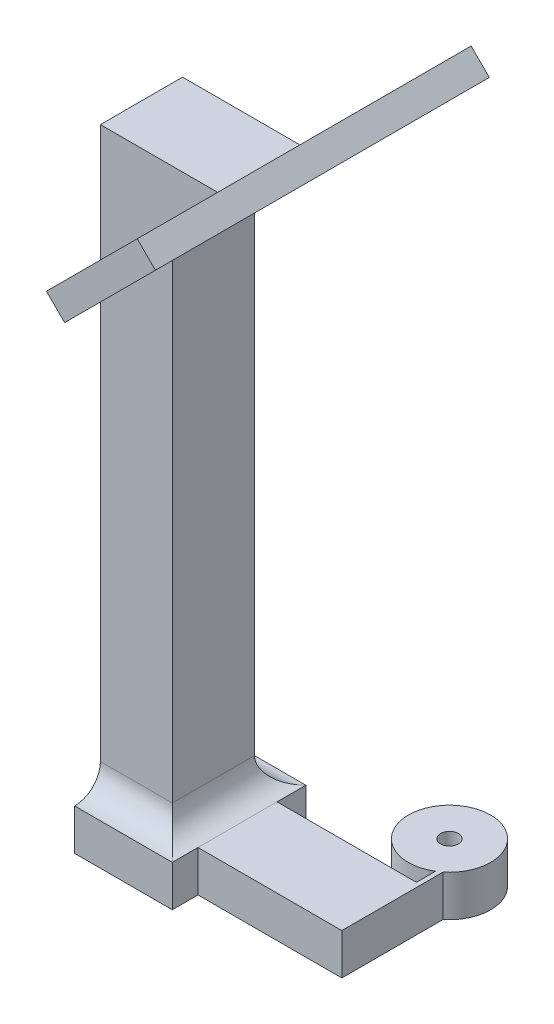
SolidWorks part; units mm, degrees
ref_plane "Front Plane" through (0, 0, 0) normal (0, 0, 1) x (1, 0, 0)
ref_plane "Top Plane" through (0, 0, 0) normal (0, 1, 0) x (1, 0, 0)
ref_plane "Right Plane" through (0, 0, 0) normal (1, 0, 0) x (0, 0, -1)
sketch "Sketch1" plane through (0, 0, 0) normal (1, 0, 0) x (0, 0, -1)
  line L0 (0, 15) -> (80, 15) construction
  line L1 (0, 0) -> (80, 0)
  line L2 (0, 0) -> (0, 30)
  line L3 (0, 30) -> (80, 30)
  line L4 (80, 0) -> (80, 30)
  line L5 (40, 15) -> (40, 30) construction
  circle A0 centre (17.5, 15) radius 1.75
  circle A1 centre (62.5, 15) radius 1.75
  dimension "D3" = 3.5
  dimension "D1" = 80
  dimension "D2" = 30
  dimension "D4" = 45
  dimension "D5" = 22.5
sketch "Sketch3" plane through (0, 0, 0) normal (0, 0, 1) x (1, 0, 0)
  line L0 (-3.5355, 33.5355) -> (0, 30)
  line L1 (0, 30) -> (17.6777, 47.6777)
  line L2 (17.6777, 47.6777) -> (14.1421, 51.2132)
  line L3 (14.1421, 51.2132) -> (-3.5355, 33.5355)
  line L4 (21.6115, 0) -> (-21.6115, 0) construction
  line L5 (0, 15) -> (0, 30) construction
  dimension "D1" = 5
  dimension "D2" = 45
  dimension "D3" = 25
  dimension "D4" = 30
  dimension "D5" = 0
extrude "Boss-Extrude2" add sketch "Sketch3" against normal blind 65
sketch "Sketch4" plane through (-18.5355, 18.5355, 0) normal (-0.7071, 0.7071, 0) x (0, 0, 1)
  line L0 (-65, 33.7132) -> (0, 33.7132) construction
  line L1 (-65, 46.2132) -> (-65, 21.2132) construction
  line L2 (0, 46.2132) -> (0, 21.2132) construction
  line L3 (-32.5, 46.2132) -> (-32.5, 21.2132) construction
  line L4 (-65, 46.2132) -> (0, 46.2132) construction
  line L5 (-65, 21.2132) -> (0, 21.2132) construction
  circle A0 centre (-10, 33.7132) radius 1.75
  circle A1 centre (-55, 33.7132) radius 1.75
  point P16 (-32.5, 33.7132)
  dimension "D3" = 3.5
  dimension "D1" = 45
  dimension "D2" = 22.5
extrude "Cut-Extrude1" cut sketch "Sketch4" against normal through all both and the other way through all
sketch "Sketch5" plane through (-15, 15, 0) normal (0.7071, -0.7071, 0) x (0, 0, -1)
  circle A0 centre (50.4624, 33.7132) radius 2 construction
  circle A1 centre (50.4624, 33.7132) radius 2 construction
sketch "Sketch6" plane through (-18.5355, 18.5355, 0) normal (-0.7071, 0.7071, 0) x (0.7071, 0.7071, 0)
  line L0 (46.2132, 32.5) -> (21.2132, 32.5) construction
  line L1 (46.2132, 65) -> (46.2132, 0) construction
  line L2 (21.2132, 65) -> (21.2132, 0) construction
  point P6 (33.7132, 32.5)
sketch "Sketch8" plane through (0, 0, -65) normal (0, 0, -1) x (-1, 0, 0)
  line L0 (-5.3033, 42.3744) -> (17.5355, 42.3744)
  line L1 (17.5355, 42.3744) -> (17.5355, 30)
  line L2 (17.5355, 30) -> (0, 30)
  line L3 (3.5355, 33.5355) -> (0, 30) construction
  line L4 (-14.1421, 51.2132) -> (3.5355, 33.5355) construction
  line L5 (3.5355, 33.5355) -> (0, 30)
  line L6 (-5.3033, 42.3744) -> (3.5355, 33.5355)
  dimension "D1" = 14
extrude "Boss-Extrude3" add sketch "Sketch8" along normal blind 8 and the other way blind 8 from offset 32.5 contours L1 L2 L5 L6 L0 offset against normal yes
sketch "Sketch9" plane through (0, 30, 0) normal (0, -1, 0) x (1, 0, 0)
  line L1 (-17.5355, -40.5) -> (-3.5355, -40.5)
  line L2 (-17.5355, -40.5) -> (-17.5355, -24.5)
  line L3 (-17.5355, -24.5) -> (-3.5355, -24.5)
  line L4 (-3.5355, -40.5) -> (-3.5355, -24.5)
extrude "Boss-Extrude4" add sketch "Sketch9" along normal blind 100
sketch "Sketch10" plane through (0, -70, 0) normal (0, -1, 0) x (1, 0, 0)
  line L11 (29.4659, -24.5) -> (29.4659, -44.2174)
  line L32 (28.5893, -39.8895) -> (28.5893, -43.6069)
  line L42 (29.4659, -24.5) -> (1.4645, -24.5)
  line L43 (1.4645, -39.8895) -> (28.5893, -39.8895)
  line L45 (-17.5355, -24.5) -> (-17.5355, -40.5)
  line L46 (-17.5355, -40.5) -> (-3.5355, -40.5)
  line L48 (-3.5355, -40.5) -> (-3.5355, -24.5)
  line L52 (-3.5355, -24.5) -> (-17.5355, -24.5)
  line L53 (-17.5355, -24.5) -> (-17.5355, -40.5) construction
  line L54 (-17.5355, -40.5) -> (-3.5355, -40.5) construction
  line L55 (1.4645, -39.8895) -> (1.4645, -45.5)
  line L56 (-3.5355, -40.5) -> (-3.5355, -24.5) construction
  line L57 (-3.5355, -24.5) -> (-17.5355, -24.5) construction
  line L58 (-17.5355, -19.5) -> (-17.5355, -45.5)
  line L62 (-22.5355, -19.5) -> (-22.5355, -45.5)
  line L63 (-22.5355, -45.5) -> (1.4645, -45.5)
  line L64 (1.4645, -45.5) -> (1.4645, -19.5)
  line L65 (1.4645, -19.5) -> (-22.5355, -19.5)
  line L67 (-17.5355, -45.5) -> (1.4645, -45.5)
  line L68 (1.4645, -45.5) -> (1.4645, -19.5)
  line L69 (1.4645, -19.5) -> (-17.5355, -19.5)
  circle A0 centre (24.4659, -50.4624) radius 1.75
  arc A2 (28.5893, -43.6069) -> (29.4659, -44.2174) centre (24.4659, -50.4624) ccw
  point P1 (24.4659, -50.4624)
  dimension "D3" = 3.5
  dimension "D5" = 3.7174
  dimension "D8" = 16
  dimension "D1" = 5
  dimension "D2" = 0
  dimension "D4" = 5
extrude "Boss-Extrude5" add sketch "Sketch10" along normal blind 8
fillet "Fillet4" radius 5 3 edges at (-10.5355, -70, -40.5) (-10.5355, -70, -24.5) (-3.5355, -70, -32.5)
